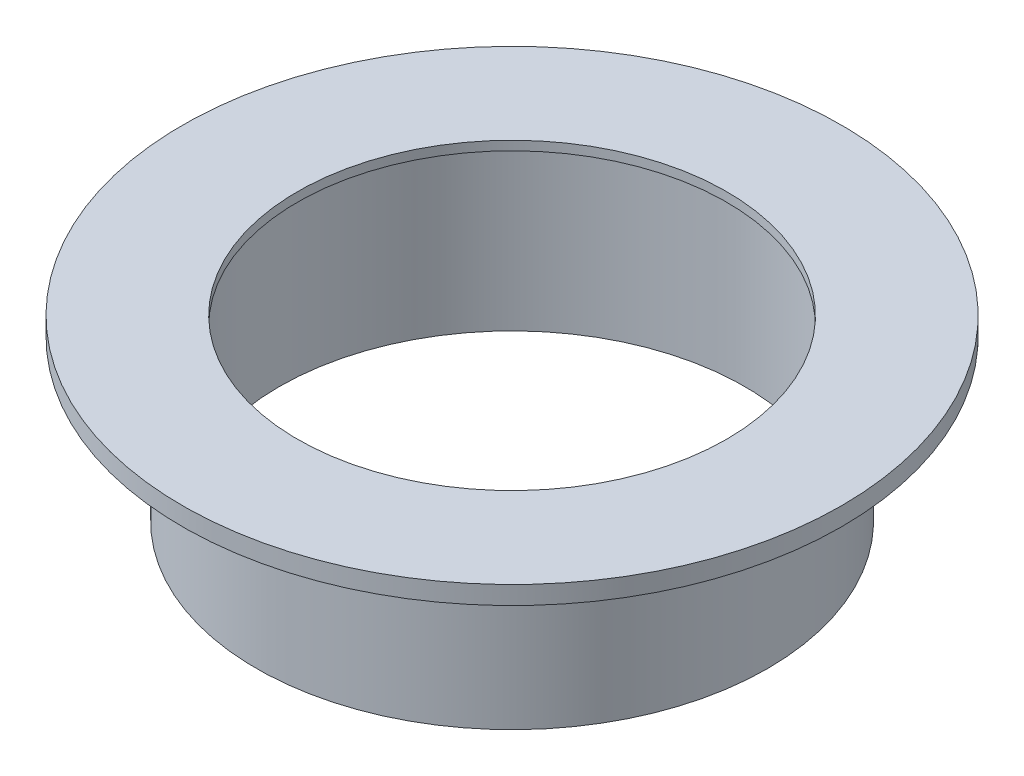
SolidWorks part; units mm, degrees
material "PET"
ref_plane "Front Plane" through (0, 0, 0) normal (0, 0, 1) x (1, 0, 0)
ref_plane "Top Plane" through (0, 0, 0) normal (0, 1, 0) x (1, 0, 0)
ref_plane "Right Plane" through (0, 0, 0) normal (1, 0, 0) x (0, 0, -1)
sketch "Sketch2" plane through (0, 0, 0) normal (0, 0, 1) x (1, 0, 0)
  line L0 (-72.2, -3.2) -> (-47, -3.2)
  line L1 (-47, -3.2) -> (-47, -5.2)
  line L2 (-47, -5.2) -> (-51, -5.2)
  line L3 (-51, -5.2) -> (-51, -42.2)
  line L4 (-51, -42.2) -> (-56, -42.2)
  line L5 (-56, -42.2) -> (-56, -7.2)
  line L6 (-56, -7.2) -> (-72.2, -7.2)
  line L7 (-72.2, -7.2) -> (-72.2, -3.2)
  line L9 (0, 0) -> (0, 30.013) construction
sketch "Sketch3" plane through (0, 0, 0) normal (0, 0, 1) x (1, 0, 0)
  line L8 (-47, -3.2) -> (-72.2, -3.2)
  line L9 (-47, -5.2) -> (-47, -3.2)
  line L10 (-51, -5.2) -> (-47, -5.2)
  line L11 (-51, -42.2) -> (-51, -5.2)
  line L12 (-56, -42.2) -> (-51, -42.2)
  line L13 (-56, -7.2) -> (-56, -42.2)
  line L14 (-72.2, -7.2) -> (-56, -7.2)
  line L15 (-72.2, -3.2) -> (-72.2, -7.2)
  line L16 (-47, -3.2) -> (-72.2, -3.2)
  line L17 (-47, -5.2) -> (-47, -3.2)
  line L18 (-51, -5.2) -> (-47, -5.2)
  line L19 (-51, -42.2) -> (-51, -5.2)
  line L20 (-56, -42.2) -> (-51, -42.2)
  line L21 (-56, -7.2) -> (-56, -42.2)
  line L22 (-72.2, -7.2) -> (-56, -7.2)
  line L23 (-72.2, -3.2) -> (-72.2, -7.2)
  dimension "D1" = 0
revolve "FRA400 100mm" add sketch "Sketch3" angle 360 about L9
